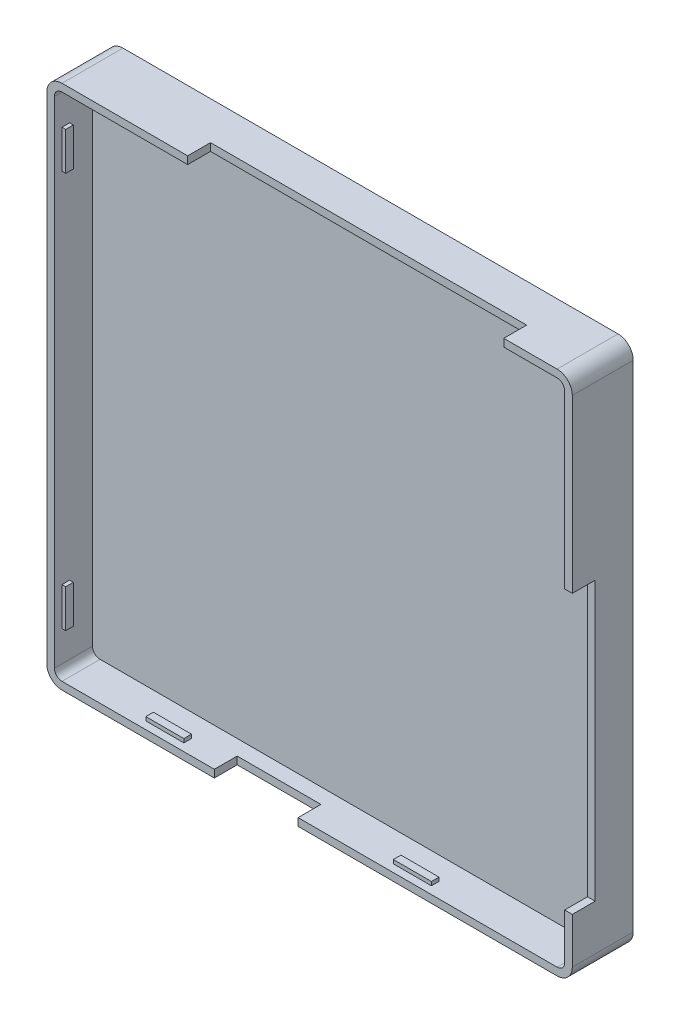
SolidWorks part; units mm, degrees
ref_plane "Plan de face" through (0, 0, 0) normal (0, 0, 1) x (1, 0, 0)
ref_plane "Plan de dessus" through (0, 0, 0) normal (0, 1, 0) x (1, 0, 0)
ref_plane "Plan de droite" through (0, 0, 0) normal (1, 0, 0) x (0, 0, -1)
sketch "Esquisse1" plane through (0, 0, 0) normal (0, 0, 1) x (1, 0, 0)
  line L1 (2, 0) -> (67, 0)
  line L2 (0, 2) -> (0, 67)
  line L3 (2, 69) -> (67, 69)
  line L4 (69, 2) -> (69, 67)
  arc A0 (2, 0) -> (0, 2) centre (2, 2) cw
  arc A1 (67, 0) -> (69, 2) centre (67, 2) ccw
  arc A2 (67, 69) -> (69, 67) centre (67, 67) cw
  arc A3 (0, 67) -> (2, 69) centre (2, 67) cw
  point P7 (0, 0)
  point P10 (69, 0)
  point P15 (0, 69)
  dimension "D3" = 2
  dimension "D1" = 69
  dimension "D2" = 69
extrude "Boss.-Extru.1" add sketch "Esquisse1" along normal blind 8
sketch "Esquisse3" plane through (0, 0, 8) normal (0, 0, 1) x (1, 0, 0)
  line L8 (2, 1) -> (67, 1)
  line L9 (68, 2) -> (68, 67)
  line L10 (67, 68) -> (2, 68)
  line L11 (1, 67) -> (1, 2)
  line L12 (2, 1) -> (67, 1)
  line L13 (68, 2) -> (68, 67)
  line L14 (67, 68) -> (2, 68)
  line L15 (1, 67) -> (1, 2)
  arc A8 (1, 2) -> (2, 1) centre (2, 2) ccw
  arc A9 (67, 1) -> (68, 2) centre (67, 2) ccw
  arc A10 (68, 67) -> (67, 68) centre (67, 67) ccw
  arc A11 (2, 68) -> (1, 67) centre (2, 67) ccw
  arc A12 (1, 2) -> (2, 1) centre (2, 2) ccw
  arc A13 (67, 1) -> (68, 2) centre (67, 2) ccw
  arc A14 (68, 67) -> (67, 68) centre (67, 67) ccw
  arc A15 (2, 68) -> (1, 67) centre (2, 67) ccw
  dimension "D1" = 1
extrude "Enlèv. mat.-Extru.1" cut sketch "Esquisse3" against normal blind 5
sketch "Esquisse4" plane through (0, 68, 0) normal (0, -1, 0) x (1, 0, 0)
  line L0 (67, 3) -> (2, 3) construction
  line L1 (8.1797, 6) -> (13.1797, 6)
  line L2 (8.1797, 6) -> (8.1797, 7)
  line L3 (8.1797, 7) -> (13.1797, 7)
  line L4 (13.1797, 6) -> (13.1797, 7)
  dimension "D1" = 3
  dimension "D2" = 1
  dimension "D3" = 5
extrude "Boss.-Extru.3" add sketch "Esquisse4" along normal blind 0.489 contours L1 L4 L3 L2
sketch "Esquisse5" plane through (68, 0, 0) normal (-1, 0, 0) x (0, 0, 1)
  line L0 (3, 2) -> (3, 67) construction
  line L1 (6, 64) -> (7, 64)
  line L2 (6, 64) -> (6, 59)
  line L3 (6, 59) -> (7, 59)
  line L4 (7, 64) -> (7, 59)
  line L5 (3, 67) -> (8, 67) construction
  dimension "D1" = 1
  dimension "D2" = 5
  dimension "D3" = 3
  dimension "D4" = 3
extrude "Boss.-Extru.4" add sketch "Esquisse5" along normal blind 0.489
sketch "Esquisse6" plane through (1, 0, 0) normal (1, 0, 0) x (0, 0, -1)
  line L0 (-3, 67) -> (-8, 67) construction
  line L1 (-6, 63) -> (-7, 63)
  line L2 (-6, 63) -> (-6, 58)
  line L3 (-6, 58) -> (-7, 58)
  line L4 (-7, 63) -> (-7, 58)
  line L5 (-3, 67) -> (-3, 2) construction
  dimension "D1" = 1
  dimension "D2" = 5
  dimension "D3" = 4
  dimension "D4" = 3
extrude "Boss.-Extru.5" add sketch "Esquisse6" along normal blind 0.489
sketch "Esquisse7" plane through (1, 0, 0) normal (1, 0, 0) x (0, 0, -1)
  line L0 (-3, 67) -> (-3, 2) construction
  line L1 (-6, 6) -> (-7, 6)
  line L2 (-6, 6) -> (-6, 11)
  line L3 (-6, 11) -> (-7, 11)
  line L4 (-7, 6) -> (-7, 11)
  line L5 (-3, 2) -> (-8, 2) construction
  dimension "D1" = 5
  dimension "D2" = 1
  dimension "D3" = 3
  dimension "D4" = 4
extrude "Boss.-Extru.6" add sketch "Esquisse7" along normal blind 0.489
sketch "Esquisse8" plane through (0, 1, 0) normal (0, 1, 0) x (1, 0, 0)
  line L0 (2, -3) -> (67, -3) construction
  line L1 (12, -6) -> (17, -6)
  line L2 (12, -6) -> (12, -7)
  line L3 (12, -7) -> (17, -7)
  line L4 (17, -6) -> (17, -7)
  line L5 (2, -3) -> (2, -8) construction
  point P6 (12, -6.5)
  dimension "D1" = 1
  dimension "D2" = 5
  dimension "D3" = 3
  dimension "D4" = 10
extrude "Boss.-Extru.7" add sketch "Esquisse8" along normal blind 0.489
sketch "Esquisse9" plane through (0, 1, 0) normal (0, 1, 0) x (1, 0, 0)
  line L0 (2, -3) -> (67, -3) construction
  line L1 (49.5, -6) -> (44.5, -6)
  line L2 (49.5, -6) -> (49.5, -7)
  line L3 (49.5, -7) -> (44.5, -7)
  line L4 (44.5, -6) -> (44.5, -7)
  line L5 (67, -3) -> (67, -8) construction
  dimension "D1" = 5
  dimension "D2" = 1
  dimension "D3" = 3
  dimension "D4" = 17.5
extrude "Boss.-Extru.8" add sketch "Esquisse9" along normal blind 0.489
sketch "Esquisse10" plane through (68, 0, 0) normal (-1, 0, 0) x (0, 0, 1)
  line L0 (3, 2) -> (8, 2) construction
  line L1 (5, 8) -> (8, 8)
  line L2 (5, 8) -> (5, 44.5)
  line L3 (5, 44.5) -> (8, 44.5)
  line L4 (8, 8) -> (8, 44.5)
  line L5 (3, 2) -> (3, 67) construction
  dimension "D1" = 36.5
  dimension "D2" = 6
  dimension "D3" = 3
  dimension "D4" = 2
extrude "Enlèv. mat.-Extru.3" cut sketch "Esquisse10" against normal through all contours L2 L1 L4 L3
sketch "Esquisse11" plane through (0, 68, 0) normal (0, -1, 0) x (1, 0, 0)
  line L0 (67, 3) -> (67, 8) construction
  line L1 (60, 5) -> (18.5, 5)
  line L2 (60, 5) -> (60, 8)
  line L3 (60, 8) -> (18.5, 8)
  line L4 (18.5, 5) -> (18.5, 8)
  line L5 (67, 3) -> (2, 3) construction
  dimension "D1" = 7
  dimension "D2" = 41.5
  dimension "D3" = 3
  dimension "D4" = 2
extrude "Enlèv. mat.-Extru.4" cut sketch "Esquisse11" against normal through all
sketch "Esquisse12" plane through (0, 1, 0) normal (0, 1, 0) x (1, 0, 0)
  line L0 (2, -3) -> (2, -8) construction
  line L1 (22, -5) -> (33, -5)
  line L2 (22, -5) -> (22, -8)
  line L3 (22, -8) -> (33, -8)
  line L4 (33, -5) -> (33, -8)
  line L5 (2, -3) -> (67, -3) construction
  dimension "D1" = 11
  dimension "D2" = 20
  dimension "D3" = 3
  dimension "D4" = 2
extrude "Enlèv. mat.-Extru.5" cut sketch "Esquisse12" against normal through all
ref_plane "Plan3" through (2, 1, 3) normal (1, 0, 0) x (0, 0, -1)
